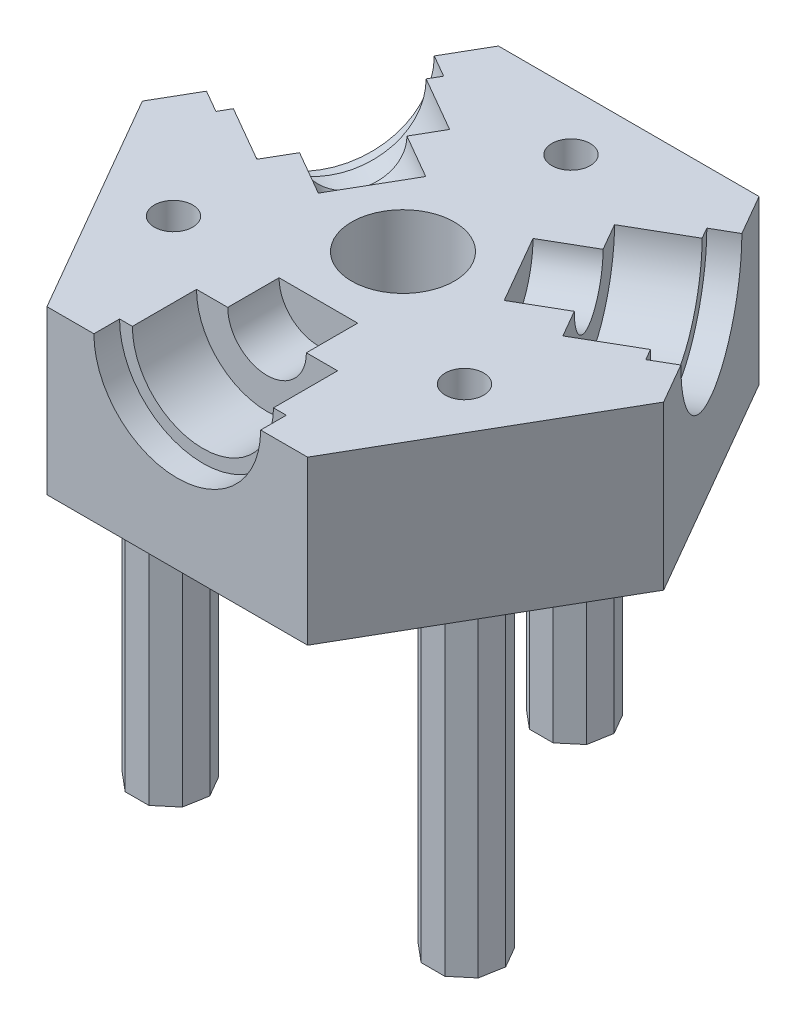
SolidWorks part; units mm, degrees
ref_plane "Front Plane" through (0, 0, 0) normal (0, 0, 1) x (1, 0, 0)
ref_plane "Top Plane" through (0, 0, 0) normal (0, 1, 0) x (1, 0, 0)
ref_plane "Right Plane" through (0, 0, 0) normal (1, 0, 0) x (0, 0, -1)
sketch "Sketch1" plane through (0, 0, 0) normal (0, 1, 0) x (1, 0, 0)
  line L1 (10.16, -17.5976) -> (20.32, 0)
  line L2 (20.32, 0) -> (10.16, 17.5976)
  line L3 (10.16, 17.5976) -> (-10.16, 17.5976)
  line L4 (-10.16, 17.5976) -> (-20.32, 0)
  line L5 (-20.32, 0) -> (-10.16, -17.5976)
  line L6 (-10.16, -17.5976) -> (10.16, -17.5976)
  circle A0 centre (0, 0) radius 17.5976 construction
  dimension "D1" = 20.32
extrude "Boss-Extrude1" add sketch "Sketch1" along normal blind 12.7 contours L4 L5 L6 L1 L2 L3
sketch "Sketch2" plane through (0, 0, 0) normal (0, -1, 0) x (1, 0, 0)
  circle A0 centre (0, 0) radius 4
  circle A1 centre (0, 0) radius 5.5
  dimension "D1" = 8
  dimension "D2" = 11
extrude "Boss-Extrude2" add sketch "Sketch2" along normal blind 3.5
sketch "Sketch5" plane through (0, 12.7, 0) normal (0, 1, 0) x (1, 0, 0)
  line L14 (0, -17.5976) -> (0, -6.5976)
  line L15 (-10.16, -17.5976) -> (10.16, -17.5976) construction
  line L16 (0, -6.5976) -> (-3.0653, -6.5976)
  line L17 (-3.0653, -6.5976) -> (-3.0653, -10.5976)
  line L18 (-3.0653, -10.5976) -> (-5.5, -10.5976)
  line L19 (-5.5, -10.5976) -> (-5.5, -15.5976)
  line L20 (-5.5, -15.5976) -> (-6.5, -15.5976)
  line L21 (-6.5, -15.5976) -> (-6.5, -17.5976)
  line L22 (-6.5, -17.5976) -> (0, -17.5976)
  dimension "D1" = 6.5
  dimension "D2" = 5.5
  dimension "D3" = 2
  dimension "D4" = 5
  dimension "D5" = 4
  dimension "D6" = 3.0653
revolve "Cut-Revolve1" cut sketch "Sketch5" angle 360 about L14
pattern_circular "CirPattern1" count 3 over 360 about axis through (0, -3.5, 0) along (0, 1, 0) of "Cut-Revolve1" reverse direction yes
sketch "Sketch6" plane through (0, 12.7, 0) normal (0, 1, 0) x (1, 0, 0)
  circle A0 centre (0, 0) radius 4
  dimension "D1" = 8
extrude "Cut-Extrude1" cut sketch "Sketch6" against normal through all
sketch "Random Circles" plane through (0, 12.7, 0) normal (0, 1, 0) x (1, 0, 0)
  line L0 (10.16, 17.5976) -> (-10.16, 17.5976) construction
  line L1 (-20.32, 0) -> (-10.16, -17.5976) construction
  line L2 (10.16, -17.5976) -> (20.32, 0) construction
  circle A0 centre (0, 13.0976) radius 1.5
  circle A1 centre (11.3429, -6.5488) radius 1.5
  circle A2 centre (-11.3429, -6.5488) radius 1.5
  point P11 (0, 0)
  dimension "D1" = 3
  dimension "D2" = 3
  dimension "D4" = 3
  dimension "D5" = 3
  dimension "D3" = 3
sketch "Sketch8" plane through (0, 0, 0) normal (0, 1, 0) x (1, 0, 0)
  line L9 (10.16, 17.5976) -> (-10.16, 17.5976) construction
  line L19 (-1.7375, 15.3916) -> (-2.6619, 13.7904)
  line L20 (-2.6619, 13.7904) -> (-2.3409, 11.9695)
  line L21 (-2.3409, 11.9695) -> (-0.9245, 10.781)
  line L22 (-0.9245, 10.781) -> (0.9245, 10.781)
  line L23 (0.9245, 10.781) -> (2.3409, 11.9695)
  line L24 (2.3409, 11.9695) -> (2.6619, 13.7904)
  line L25 (2.6619, 13.7904) -> (1.7375, 15.3916)
  line L26 (1.7375, 15.3916) -> (0, 16.024)
  line L27 (0, 16.024) -> (-1.7375, 15.3916)
  line L28 (14.1983, -6.1911) -> (13.2738, -4.5899)
  line L29 (13.2738, -4.5899) -> (11.5363, -3.9575)
  line L30 (11.5363, -3.9575) -> (9.7989, -4.5899)
  line L31 (9.7989, -4.5899) -> (8.8744, -6.1911)
  line L32 (8.8744, -6.1911) -> (9.1954, -8.012)
  line L33 (9.1954, -8.012) -> (10.6118, -9.2005)
  line L34 (10.6118, -9.2005) -> (12.4608, -9.2005)
  line L35 (12.4608, -9.2005) -> (13.8772, -8.012)
  line L36 (13.8772, -8.012) -> (14.1983, -6.1911)
  line L37 (-12.4608, -9.2005) -> (-10.6118, -9.2005)
  line L38 (-10.6118, -9.2005) -> (-9.1954, -8.012)
  line L39 (-9.1954, -8.012) -> (-8.8744, -6.1911)
  line L40 (-8.8744, -6.1911) -> (-9.7989, -4.5899)
  line L41 (-9.7989, -4.5899) -> (-11.5363, -3.9575)
  line L42 (-11.5363, -3.9575) -> (-13.2738, -4.5899)
  line L43 (-13.2738, -4.5899) -> (-14.1983, -6.1911)
  line L44 (-14.1983, -6.1911) -> (-13.8772, -8.012)
  line L45 (-13.8772, -8.012) -> (-12.4608, -9.2005)
  circle A0 centre (11.5363, -6.6605) radius 2.54 construction
  circle A1 centre (-11.5363, -6.6605) radius 2.54 construction
  circle A2 centre (0, 13.321) radius 2.54 construction
  point P0 (0, 17.5976)
  point P37 (0, 0)
  dimension "D1" = 23.0726
  dimension "D2" = 3
  dimension "D6" = 5.08
  dimension "D3" = 1.5736
extrude "Boss-Extrude3" add sketch "Sketch8" against normal blind 25.4
extrude "Cut-Extrude2" cut sketch "Random Circles" against normal blind 2.54
